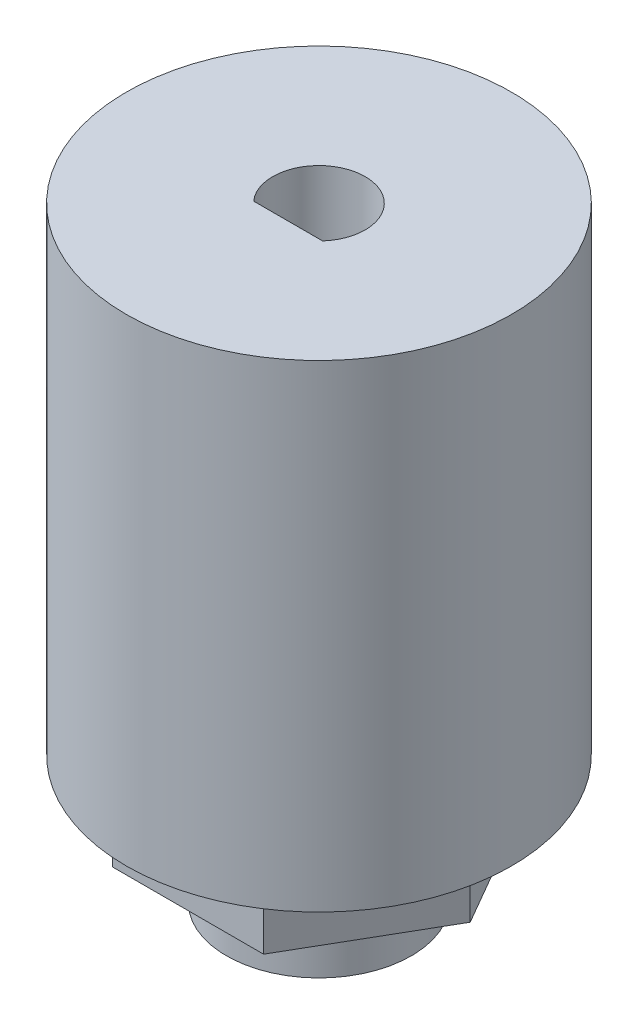
SolidWorks part; units mm, degrees
ref_plane "Front Plane" through (0, 0, 0) normal (0, 0, 1) x (1, 0, 0)
ref_plane "Top Plane" through (0, 0, 0) normal (0, 1, 0) x (1, 0, 0)
ref_plane "Right Plane" through (0, 0, 0) normal (1, 0, 0) x (0, 0, -1)
sketch "Sketch1" plane through (0, 0, 0) normal (0, 1, 0) x (1, 0, 0)
  circle A0 centre (0, 0) radius 6
  dimension "D1" = 12
extrude "Boss-Extrude1" add sketch "Sketch1" along normal blind 3.8
sketch "Sketch2" plane through (0, 3.8, 0) normal (0, 1, 0) x (1, 0, 0)
  line L1 (9.815, 0) -> (4.9075, 8.5)
  line L2 (4.9075, 8.5) -> (-4.9075, 8.5)
  line L3 (-4.9075, 8.5) -> (-9.815, 0)
  line L4 (-9.815, 0) -> (-4.9075, -8.5)
  line L5 (-4.9075, -8.5) -> (4.9075, -8.5)
  line L6 (4.9075, -8.5) -> (9.815, 0)
  circle A0 centre (0, 0) radius 8.5 construction
  dimension "D1" = 17
extrude "Boss-Extrude2" add sketch "Sketch2" along normal blind 4.5
sketch "Sketch3" plane through (0, 8.3, 0) normal (0, 1, 0) x (1, 0, 0)
  circle A0 centre (0, 0) radius 12.5
  dimension "D1" = 25
extrude "Boss-Extrude3" add sketch "Sketch3" along normal blind 4
sketch "Sketch4" plane through (0, 12.3, 0) normal (0, 1, 0) x (1, 0, 0)
  circle A0 centre (0, 0) radius 12.5
  dimension "D1" = 25
extrude "Boss-Extrude4" add sketch "Sketch4" along normal blind 27
sketch "Sketch5" plane through (0, 39.3, 0) normal (0, 1, 0) x (1, 0, 0)
  line L0 (-2.2361, -2) -> (2.2361, -2)
  circle A0 centre (0, 0) radius 3
  point P3 (0, 3)
  dimension "D1" = 6
  dimension "D2" = 5
extrude "Cut-Extrude1" cut sketch "Sketch5" against normal through all contours L0 A0 region at (0, 39.3, -0.296)
sketch "Sketch6" plane through (0, 0, 0) normal (0, -1, 0) x (1, 0, 0)
  circle A0 centre (0, 0) radius 3.6
  dimension "D1" = 7.2
extrude "Cut-Extrude2" cut sketch "Sketch6" against normal blind 6
